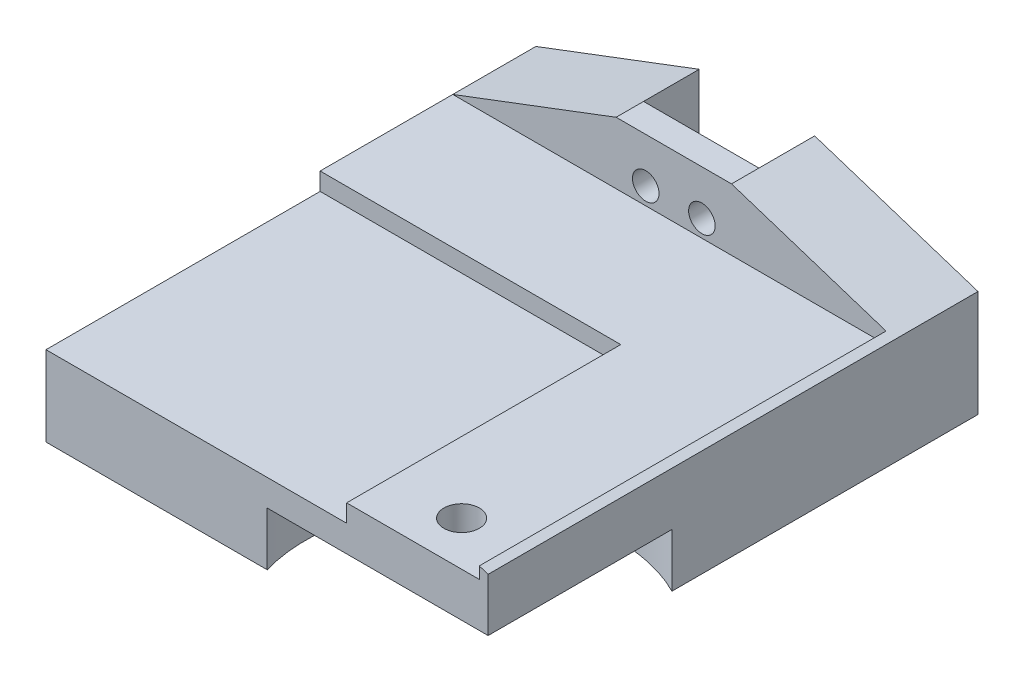
SolidWorks part; units mm, degrees
ref_plane "Front Plane" through (0, 0, 0) normal (0, 0, 1) x (1, 0, 0)
ref_plane "Top Plane" through (0, 0, 0) normal (0, 1, 0) x (1, 0, 0)
ref_plane "Right Plane" through (0, 0, 0) normal (1, 0, 0) x (0, 0, -1)
sketch "OutlineSketch2" plane through (0, 0, 0) normal (0, 1, 0) x (1, 0, 0)
  line L1 (0, 0) -> (50, 0)
  line L2 (0, 0) -> (0, 55.4)
  line L3 (0, 55.4) -> (50, 55.4)
  line L4 (50, 0) -> (50, 55.4)
  circle A0 centre (42, 5) radius 2
  dimension "D5" = 4
  dimension "D1" = 5
  dimension "D2" = 8
  dimension "D3" = 50.4
  dimension "D4" = 50
extrude "OutlineBoss-Extrude1" add sketch "OutlineSketch2" along normal blind 18.05
sketch "BuildPlateCutoutSketch1" plane through (0, 18.05, 0) normal (0, 1, 0) x (1, 0, 0)
  line L1 (0, 0) -> (49, 0)
  line L2 (0, 0) -> (0, 46)
  line L3 (0, 46) -> (49, 46)
  line L4 (49, 0) -> (49, 46)
  dimension "D1" = 7
  dimension "D2" = 41
extrude "BuildPlateCutoutCut-Extrude7" cut sketch "BuildPlateCutoutSketch1" against normal blind 7
sketch "MicroSwitchSketch9" plane through (0, 0, -55.4) normal (0, 0, -1) x (-1, 0, 0)
  line L0 (-50, 18.05) -> (0, 18.05) construction
  line L1 (-31.525, 18.05) -> (-18.475, 18.05)
  line L2 (-31.525, 18.05) -> (-31.525, 6)
  line L3 (-31.525, 6) -> (-18.475, 6)
  line L4 (-18.475, 18.05) -> (-18.475, 6)
  line L6 (0, 18.05) -> (0, 0) construction
  dimension "D1" = 13.05
  dimension "D2" = 12.05
  dimension "D3" = 18.475
extrude "MicroSwitchCut-Extrude6" cut sketch "MicroSwitchSketch9" against normal blind 6.3
sketch "MicroSwitchMountingHolesSketch10" plane through (0, 0, -49.1) normal (0, 0, -1) x (-1, 0, 0)
  line L3 (-31.525, 18.05) -> (-31.525, 6) construction
  line L4 (-18.475, 6) -> (-18.475, 18.05) construction
  line L6 (-31.525, 6) -> (-18.475, 6) construction
  circle A0 centre (-28.175, 13) radius 1.5
  circle A1 centre (-21.825, 13) radius 1.5
  dimension "D2" = 3.35
  dimension "D3" = 3.35
  dimension "D4" = 7
extrude "MicroSwitchMountingHolesCut-Extrude4" cut sketch "MicroSwitchMountingHolesSketch10" against normal blind 3.1
sketch "CableCutSketch11" plane through (0, 6, 0) normal (0, 1, 0) x (1, 0, 0)
  line L0 (24.125, 55.4) -> (24.125, 53.65)
  line L2 (24.125, 53.65) -> (23.125, 53.65)
  line L3 (23.125, 53.65) -> (23.125, 51.9)
  line L4 (23.125, 51.9) -> (26.875, 51.9)
  line L5 (26.875, 51.9) -> (26.875, 53.65)
  line L6 (26.875, 53.65) -> (25.875, 53.65)
  line L7 (25.875, 53.65) -> (25.875, 55.4)
  line L8 (25.875, 55.4) -> (24.125, 55.4)
  line L11 (31.525, 55.4) -> (18.475, 55.4) construction
  line L12 (31.525, 49.1) -> (31.525, 55.4) construction
  dimension "D1" = 1.75
  dimension "D2" = 3.75
  dimension "D3" = 1.75
  dimension "D4" = 4.65
extrude "CableCutCut-Extrude5" cut sketch "CableCutSketch11" against normal through all
sketch "HeatMatCutSketch3" plane through (0, 11.05, 0) normal (0, 1, 0) x (1, 0, 0)
  line L0 (0, 0) -> (49, 0) construction
  line L1 (0, 0) -> (34, 0)
  line L2 (0, 0) -> (0, 31)
  line L3 (0, 31) -> (34, 31)
  line L4 (34, 0) -> (34, 31)
  line L5 (0, 46) -> (0, 0) construction
  line L6 (49, 46) -> (0, 46) construction
  line L7 (49, 0) -> (49, 46) construction
  dimension "D1" = 15
  dimension "D2" = 15
extrude "HeatMatCut-Extrude8" cut sketch "HeatMatCutSketch3" against normal blind 2
sketch "BallJointCutoutSketch4" plane through (0, 0, 0) normal (0, -1, 0) x (1, 0, 0)
  line L0 (25.0209, 0) -> (50, 0)
  line L2 (50, 0) -> (50, -20.7889)
  line L4 (50, 0) -> (50, -55.4) construction
  arc A0 (25.0209, 0) -> (50, -20.7889) centre (42, -5) ccw
  dimension "D1" = 35.4
extrude "BallJointCut-Extrude9" cut sketch "BallJointCutoutSketch4" against normal blind 6.05
chamfer "Chamfer1" distance 7 distance2 18.475 1 edges at (0, 18.05, -50.7) first distance on face at (0, 9.5375, -33.1)
chamfer "Chamfer2" distance 6 distance2 18.475 1 edges at (50, 18.05, -27.7) first distance on face at (50, 8.0333, -25.3963)
equation "\"BuildPlateStandoffHolesDistanceFromLeftOrRightSide\"= 7mm"
equation "\"BuildPlateStandoffHolesDistanceFromBackSide\"= 41mm"
equation "\"BedSpringHoleSize\"= \"M4HoleDiameter\""
equation "\"D5@OutlineSketch2\" = \"BedSpringHoleSize\""
equation "\"D1@OutlineBoss-Extrude1\" = \"BuildPlateZEndstopDepth\""
equation "\"BuildPlateStandoffHolesDistanceFromFront\"= 7mm"
equation "\"M4HoleDiameter\"= 4mm"
equation "\"D1@OutlineSketch2\"=\"RightedgeSize\"+ \"BedSpringHoleSize\""
equation "\"D2@OutlineSketch2\"=  \"BuildPlateStandoffHolesDistanceFromFront\" + \"RightedgeSize\""
equation "\"D3@OutlineSketch2\" = \"BuildPlateStandoffHolesDistanceFromBackSide\" + \"BackEdgeSize\""
equation "\"RightedgeSize\"= 1mm"
equation "\"MicroSwitchLength\"= 13.05mm"
equation "\"MicroSwitchHeight\"= 6.55mm"
equation "\"MicroSwitchHoleOffsetFromSide\"= 3.35mm"
equation "\"MicroSwutchTerminalHeight\"= 3.5mm"
equation "\"MicroSwitchExtraMountingHeight\"= 2mm"
equation "\"MicroSwitchDepth\"= 2.8mm"
equation "\"BuildPlateZEndstopDepth\"= \"BuildPlateDepth\" + \"MicroSwutchTerminalHeight\" + \"MicroSwitchHeight\""
equation "\"BackEdgeSize\"= \"EndStopCableDepth\" * 2 + \"MicroSwitchDepth\" + \"M2HeatInsertHoleDepth\""
equation "\"MicroSwitchHoleOffsetFromBottom\"= 7mm"
equation "\"M2HeatInsertHoleDiameter\"= 3mm'Spec"
equation "\"M2HeatInsertHoleDepth\"= 3.1mm'Spec"
equation "\"BuildPlateEndStopHolderWidth\"= 50mm"
equation "\"D4@OutlineSketch2\"=\"BuildPlateEndStopHolderWidth\""
equation "\"D1@MicroSwitchSketch9\" = \"MicroSwitchLength\""
equation "\"D1@MicroSwitchMountingHolesSketch10\" = \"M2HeatInsertHoleDiameter\""
equation "\"D1@MicroSwitchMountingHolesCut-Extrude4\" = \"M2HeatInsertHoleDepth\""
equation "\"EndStopCableWidth\"=3.75"
equation "\"D2@CableCutSketch11\" = \"EndStopCableWidth\""
equation "\"EndStopCableDepth\"=1.75"
equation "\"D1@CableCutSketch11\" = \"EndStopCableDepth\""
equation "\"D3@CableCutSketch11\" = \"EndStopCableDepth\""
equation "\"BuildPlateDepth\"= 8mm'Spec"
equation "\"D1@MicroSwitchCut-Extrude6\"=\"BackEdgeSize\" - \"M2HeatInsertHoleDepth\""
equation "\"D2@MicroSwitchMountingHolesSketch10\"=\"MicroSwitchHoleOffsetFromSide\""
equation "\"D3@MicroSwitchMountingHolesSketch10\"=\"MicroSwitchHoleOffsetFromSide\""
equation "\"D4@MicroSwitchMountingHolesSketch10\"=\"MicroSwitchHoleOffsetFromBottom\""
equation "\"D1@BuildPlateCutoutSketch1\" = \"BuildPlateStandoffHolesDistanceFromLeftOrRightSide\""
equation "\"D2@BuildPlateCutoutSketch1\" = \"BuildPlateStandoffHolesDistanceFromBackSide\""
equation "\"D1@BuildPlateCutoutCut-Extrude7\"=\"BuildPlateDepth\"-1mm"
equation "\"D2@MicroSwitchSketch9\"=\"MicroSwitchExtraMountingHeight\"+ \"MicroSwutchTerminalHeight\" + \"MicroSwitchHeight\""
equation "\"BallJointDiameter\"= 1in"
equation "\"D1@BallJointCut-Extrude9\"=\"BuildPlateZEndstopDepth\" - \"BuildPlateDepth\" -1mm - 3mm"
equation "\"D1@Chamfer1\"=7"
equation "\"D3@Chamfer1\"=(\"BuildPlateEndStopHolderWidth\"-\"MicroSwitchLength\")/2"
equation "\"D3@Chamfer2\"=(\"BuildPlateEndStopHolderWidth\"-\"MicroSwitchLength\")/2"
equation "\"D3@MicroSwitchSketch9\"=(\"BuildPlateEndStopHolderWidth\"-\"MicroSwitchLength\")/2"
equation "\"D4@CableCutSketch11\"=(\"MicroSwitchLength\"-\"EndStopCableWidth\")/2"
equation "\"HeatMatBuildPlateBorderSize\"=15"
equation "\"D1@HeatMatCutSketch3\"=\"HeatMatBuildPlateBorderSize\""
equation "\"D2@HeatMatCutSketch3\"=\"HeatMatBuildPlateBorderSize\""
equation "\"D1@BallJointCutoutSketch4\"=\"BallJointDiameter\" + 10mm"
